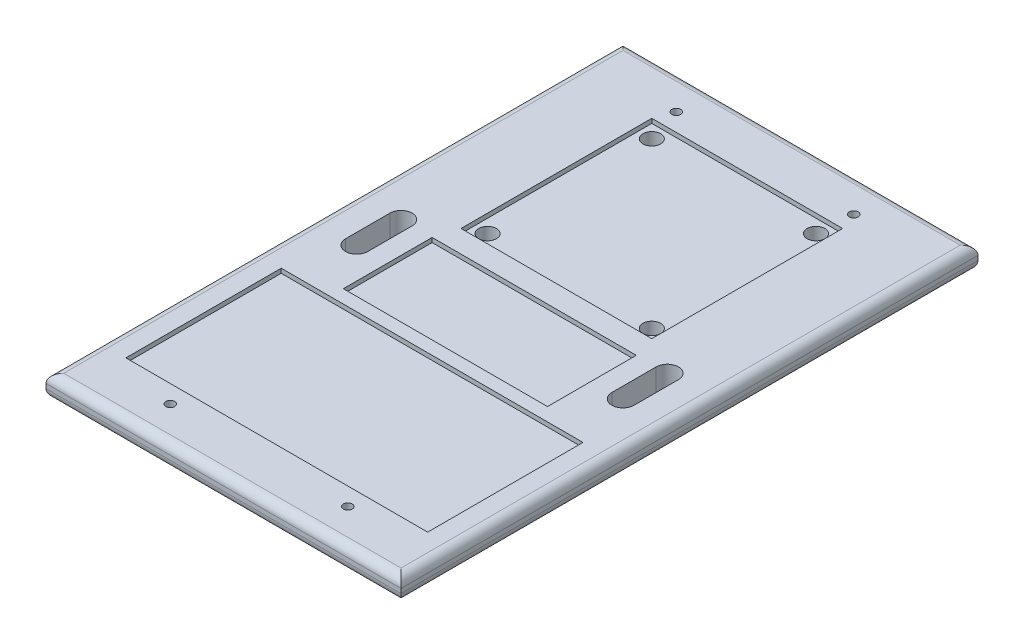
SolidWorks part; units mm, degrees
ref_plane "Front Plane" through (0, 0, 0) normal (0, 0, 1) x (1, 0, 0)
ref_plane "Top Plane" through (0, 0, 0) normal (0, 1, 0) x (1, 0, 0)
ref_plane "Right Plane" through (0, 0, 0) normal (1, 0, 0) x (0, 0, -1)
sketch "Sketch2" plane through (0, 0, 0) normal (0, 1, 0) x (1, 0, 0)
  line L0 (-40, 130) -> (-40, 0) construction
  line L1 (0, 0) -> (-80, 0)
  line L2 (0, 0) -> (0, 130)
  line L3 (0, 130) -> (-80, 130)
  line L4 (-80, 0) -> (-80, 130)
  line L5 (0, 65) -> (-80, 65) construction
  line L6 (-8, 28) -> (-8, 8) construction
  line L7 (-4, 28) -> (-4, 8)
  line L8 (-12, 28) -> (-12, 8)
  line L9 (-8, 102) -> (-8, 122) construction
  line L10 (-4, 102) -> (-4, 122)
  line L11 (-12, 102) -> (-12, 122)
  line L12 (-72, 102) -> (-72, 122) construction
  line L13 (-76, 102) -> (-76, 122)
  line L14 (-68, 102) -> (-68, 122)
  line L15 (-72, 28) -> (-72, 8) construction
  line L16 (-76, 28) -> (-76, 8)
  line L17 (-68, 28) -> (-68, 8)
  arc A0 (-4, 28) -> (-12, 28) centre (-8, 28) ccw
  arc A1 (-12, 8) -> (-4, 8) centre (-8, 8) ccw
  arc A2 (-4, 102) -> (-12, 102) centre (-8, 102) cw
  arc A3 (-12, 122) -> (-4, 122) centre (-8, 122) cw
  arc A4 (-76, 102) -> (-68, 102) centre (-72, 102) ccw
  arc A5 (-68, 122) -> (-76, 122) centre (-72, 122) ccw
  arc A6 (-76, 28) -> (-68, 28) centre (-72, 28) cw
  arc A7 (-68, 8) -> (-76, 8) centre (-72, 8) cw
  point P11 (-8, 18)
  point P16 (-4, 18)
  point P20 (-8, 112)
  point P27 (-72, 112)
  point P34 (-72, 18)
  dimension "D5" = 4
  dimension "D1" = 80
  dimension "D2" = 130
  dimension "D3" = 20
  dimension "D4" = 8
  dimension "D6" = 8
  dimension "D7" = 8
extrude "Boss-Extrude1" add sketch "Sketch2" against normal blind 3
sketch "Sketch3" plane through (0, 0, 0) normal (0, 1, 0) x (1, 0, 0)
  line L1 (-80, 0) -> (0, 0)
  line L2 (-80, 0) -> (-80, 130)
  line L3 (-80, 130) -> (0, 130)
  line L4 (0, 0) -> (0, 130)
extrude "Boss-Extrude2" add sketch "Sketch3" along normal blind 2
fillet "Fillet1" radius 2 8 edges at (-40, -3, -130) (-40, 2, -130) (-80, -3, -65) (-80, 2, -65) (0, 2, -65) (0, -3, -65) (-40, -3, 0) (-40, 2, 0)
sketch "Sketch4" plane through (0, 0, 0) normal (0, 1, 0) x (1, 0, 0)
  line L0 (-80, 65) -> (-2, 65) construction
  line L1 (-80, 130) -> (0, 130)
  line L2 (-80, 130) -> (-80, 0)
  line L3 (-80, 0) -> (0, 0)
  line L4 (0, 130) -> (0, 0)
  line L5 (0, 0) -> (-80, 0)
  line L6 (0, 0) -> (0, 130)
  line L7 (0, 130) -> (-80, 130)
  line L8 (-80, 0) -> (-80, 130)
  line L9 (-2, 2) -> (-2, 128) construction
  line L10 (-40, 130) -> (-40, 2) construction
  line L11 (-78, 2) -> (-2, 2) construction
  line L12 (-10, 70) -> (-10, 60) construction
  line L13 (-7.5, 70) -> (-7.5, 60)
  line L14 (-12.5, 70) -> (-12.5, 60)
  line L15 (-70, 70) -> (-70, 60) construction
  line L16 (-72.5, 70) -> (-72.5, 60)
  line L17 (-67.5, 70) -> (-67.5, 60)
  arc A0 (-7.5, 70) -> (-12.5, 70) centre (-10, 70) ccw
  arc A1 (-12.5, 60) -> (-7.5, 60) centre (-10, 60) ccw
  arc A2 (-72.5, 70) -> (-67.5, 70) centre (-70, 70) cw
  arc A3 (-67.5, 60) -> (-72.5, 60) centre (-70, 60) cw
  point P16 (-10, 65)
  point P25 (-70, 65)
  dimension "D1" = 10
  dimension "D2" = 5
  dimension "D3" = 8
extrude "Cut-Extrude1" cut sketch "Sketch4" against normal through all both and the other way through all contours L16 A3 L17 A2 | L14 A1 L13 A0
sketch "Sketch6" plane through (0, 2, 0) normal (0, 1, 0) x (1, 0, 0)
  line L0 (-40, 2) -> (-40, 128) construction
  line L1 (-78, 2) -> (-2, 2) construction
  line L2 (-2, 128) -> (-78, 128) construction
  line L3 (-78, 65) -> (-2, 65) construction
  line L4 (-78, 128) -> (-78, 2) construction
  line L5 (-2, 2) -> (-2, 128) construction
  line L6 (-61.5, 96.5) -> (-18.5, 96.5) construction
  line L7 (-78, 128) -> (-2, 128)
  line L8 (-78, 128) -> (-78, 2) construction
  line L9 (-78, 2) -> (-2, 2)
  line L10 (-2, 128) -> (-2, 2)
  line L11 (-6, 47) -> (-74, 47)
  line L12 (-6, 47) -> (-6, 12)
  line L13 (-6, 12) -> (-74, 12)
  line L14 (-74, 47) -> (-74, 12)
  line L15 (-6, 47) -> (-74, 12) construction
  line L16 (-6, 12) -> (-74, 47) construction
  line L17 (-18.5, 118) -> (-61.5, 118)
  line L18 (-18.5, 118) -> (-18.5, 75)
  line L19 (-18.5, 75) -> (-61.5, 75)
  line L20 (-61.5, 118) -> (-61.5, 75)
  line L21 (-18.5, 118) -> (-61.5, 75) construction
  line L22 (-18.5, 75) -> (-61.5, 118) construction
  line L23 (-17, 70) -> (-63, 70)
  line L24 (-17, 70) -> (-17, 50)
  line L25 (-17, 50) -> (-63, 50)
  line L26 (-63, 70) -> (-63, 50)
  line L27 (-17, 70) -> (-63, 50) construction
  line L28 (-17, 50) -> (-63, 70) construction
  line L29 (-40, 118) -> (-40, 75) construction
  circle A0 centre (-60, 122) radius 1
  circle A1 centre (-20, 122) radius 1
  circle A2 centre (-20, 8) radius 1
  circle A3 centre (-60, 8) radius 1
  circle A4 centre (-21.5, 115) radius 2
  circle A5 centre (-21.5, 78) radius 2
  circle A6 centre (-58.5, 78) radius 2
  circle A7 centre (-58.5, 115) radius 2
  point P26 (-40, 29.5)
  point P31 (-40, 96.5)
  point P36 (-40, 75)
  point P37 (-40, 60)
  dimension "D1" = 18
  dimension "D3" = 2
  dimension "D13" = 4
  dimension "D2" = 6
  dimension "D4" = 68
  dimension "D5" = 35
  dimension "D6" = 10
  dimension "D7" = 43
  dimension "D8" = 43
  dimension "D9" = 10
  dimension "D10" = 46
  dimension "D11" = 20
  dimension "D12" = 5
  dimension "D14" = 3
  dimension "D15" = 3
extrude "Cut-Extrude2" cut sketch "Sketch6" against normal blind 3 contours A3 | A2 | A1 | A0
extrude "Cut-Extrude3" cut sketch "Sketch6<3>" against normal blind 1 contours L11 L14 L13 L12 | L23 L26 L25 L24 | L17 L20 L19 L18 region at (-40, 2, -29.5) region at (-40, 2, -96.5) region at (-40, 2, -60)
sketch "Sketch6<3>" plane through (0, 2, 0) normal (0, 1, 0) x (1, 0, 0) same geometry as "Sketch6"
extrude "Cut-Extrude4" cut sketch "Sketch6<4>" against normal through all contours A4 | A6 | A5 | A7 region at (-21.5, 2, -115) region at (-21.5, 2, -78) region at (-58.5, 2, -78)
sketch "Sketch6<4>" plane through (0, 2, 0) normal (0, 1, 0) x (1, 0, 0) same geometry as "Sketch6"
